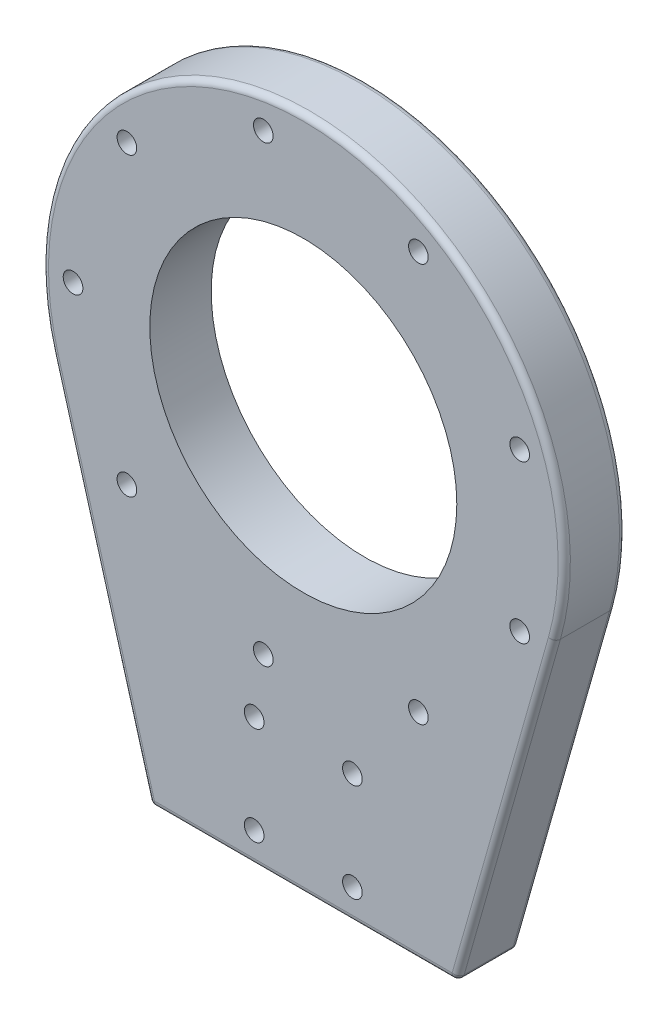
SolidWorks part; units mm, degrees
ref_plane "Front Plane" through (0, 0, 0) normal (0, 0, 1) x (1, 0, 0)
ref_plane "Top Plane" through (0, 0, 0) normal (0, 1, 0) x (1, 0, 0)
ref_plane "Right Plane" through (0, 0, 0) normal (1, 0, 0) x (0, 0, -1)
sketch "Sketch1" plane through (0, 0, 0) normal (0, 0, 1) x (1, 0, 0)
  line L0 (-40.8812, -11.6181) -> (-25, -67.5)
  line L1 (-25, -67.5) -> (25, -67.5)
  line L2 (25, -67.5) -> (40.8812, -11.6181)
  arc A0 (40.8812, -11.6181) -> (-40.8812, -11.6181) centre (0, 0) ccw
  circle A1 centre (-37.5, 0) radius 1.6
  circle A2 centre (-28.7267, 24.1045) radius 1.6
  circle A3 centre (-6.5118, 36.9303) radius 1.6
  circle A4 centre (18.75, 32.476) radius 1.6
  circle A5 centre (35.2385, 12.8258) radius 1.6
  circle A6 centre (35.2385, -12.8258) radius 1.6
  circle A7 centre (18.75, -32.476) radius 1.6
  circle A8 centre (-6.5118, -36.9303) radius 1.6
  circle A9 centre (-28.7267, -24.1045) radius 1.6
  circle A10 centre (0, 0) radius 25
  point P1 (0, -67.5)
  point P24 (0, 0)
  dimension "D1" = 85
  dimension "D2" = 3.2
  dimension "D4" = 50
  dimension "D3" = 37.5
  dimension "D5" = 25
  dimension "D6" = 50
extrude "Boss-Extrude1" add sketch "Sketch1" along normal blind 10
fillet "Fillet3" radius 1 6 edges at (32.9406, -39.559, 0) (-32.9406, -39.559, 0) (-32.9406, -39.559, 10) (0, 42.5, 10) (0, 42.5, 0) (32.9406, -39.559, 10)
fillet "Fillet4" radius 1 8 edges at (-25, -67.5, 5) (-24.6955, -67.5, 0.2929) (25, -67.5, 5) (24.6955, -67.5, 0.2929) (0, -67.5, 0) (-24.6955, -67.5, 9.7071) (0, -67.5, 10) (24.6955, -67.5, 9.7071)
sketch "Sketch6" plane through (0, 0, 10) normal (0, 0, 1) x (1, 0, 0)
  line L0 (-24.2446, -66.5) -> (24.2446, -66.5) construction
  line L1 (-8, -62.5) -> (8, -62.5) construction
  line L2 (-8, -62.5) -> (-8, -46.5) construction
  line L3 (-8, -46.5) -> (8, -46.5) construction
  line L4 (8, -62.5) -> (8, -46.5) construction
  line L5 (-8, -62.5) -> (8, -46.5) construction
  line L6 (-8, -46.5) -> (8, -62.5) construction
  circle A0 centre (-8, -46.5) radius 1.6
  circle A1 centre (8, -46.5) radius 1.6
  circle A2 centre (8, -62.5) radius 1.6
  circle A3 centre (-8, -62.5) radius 1.6
  point P0 (0, -54.5)
  dimension "D4" = 3.2
  dimension "D5" = 3.2
  dimension "D6" = 3.2
  dimension "D7" = 3.2
  dimension "D1" = 16
  dimension "D2" = 16
  dimension "D3" = 12
extrude "Cut-Extrude3" cut sketch "Sketch6" against normal through all
